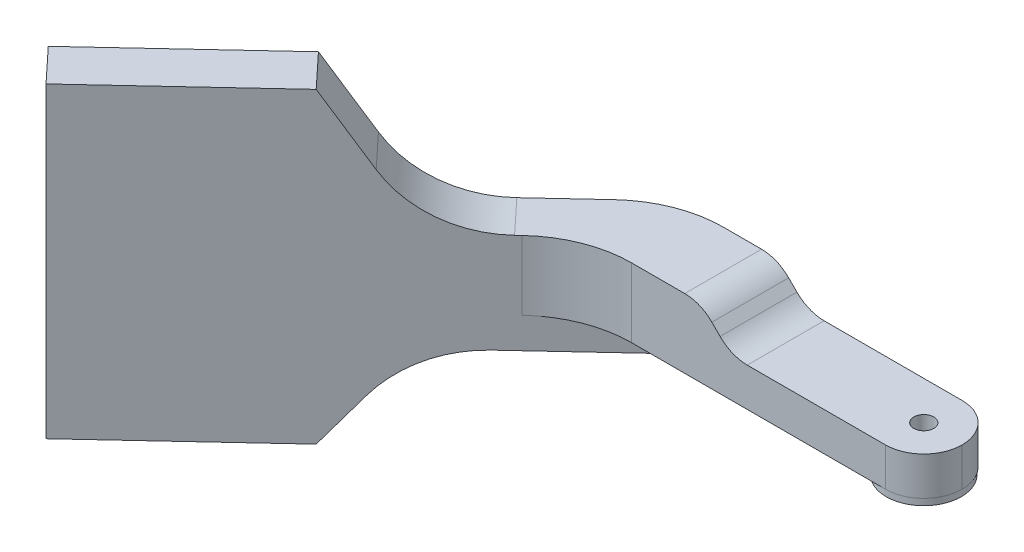
SolidWorks part; units mm, degrees
ref_plane "Front" through (0, 0, 0) normal (0, 0, 1) x (1, 0, 0)
ref_plane "Top" through (0, 0, 0) normal (0, 1, 0) x (1, 0, 0)
ref_plane "Right" through (0, 0, 0) normal (1, 0, 0) x (0, 0, -1)
sketch "Sketch1" plane through (0, 0, 0) normal (0, 1, 0) x (1, 0, 0)
  line L0 (0, 10) -> (0, 0)
  line L1 (0, 0) -> (42, 0)
  line L3 (0, 10) -> (42, 10)
  line L4 (42, 0) -> (42, 10)
  line L9 (0, 10) -> (-42.4185, -29.5559)
  line L10 (-42.4185, -29.5559) -> (-38.3265, -33.944)
  line L11 (0, 10) -> (4.092, 5.6119)
  line L12 (-38.3265, -33.944) -> (4.092, 5.6119)
  line L13 (0, 0) -> (-1.926, 0)
  line L14 (-1.926, 0) -> (0, 1.796)
  line L15 (0, 1.796) -> (0, 0)
  dimension "D1" = 10
  dimension "D2" = 42
  dimension "D3" = 223
  dimension "D4" = 58
  dimension "D5" = 6
  dimension "D6" = 270
extrude "Boss-Extrude1" add sketch "Sketch1" along normal blind 5 contours L10 L12 L1 L0 L9 | L1 L12 L11 L0 | L12 L1 L4 L3 L11 | L13 L0 L12 region at (1.364, 0, -5.8026) region at (-20.2035, 0, 12.8728) region at (21.8174, 0, -4.9666) region at (-0.642, 0, -0.5987)
fillet "Fillet1" radius 5 2 edges at (42, 2.5, 0) (42, 2.5, -10)
sketch "Sketch2" plane through (0, 5, 0) normal (0, 1, 0) x (1, 0, 0)
  circle A0 centre (37, 5) radius 1.3
extrude "Cut-Extrude1" cut sketch "Sketch2" against normal blind 10
sketch "Sketch3" plane through (0, 5, 0) normal (0, 1, 0) x (1, 0, 0)
  line L0 (-42.4185, -29.5559) -> (-38.3265, -33.944)
  line L1 (-38.3265, -33.944) -> (-20.1263, -16.972)
  line L2 (-38.3265, -33.944) -> (-1.926, 0) construction
  line L3 (-20.1263, -16.972) -> (-24.2183, -12.5839)
  line L4 (0, 10) -> (-42.4185, -29.5559) construction
  line L5 (-24.2183, -12.5839) -> (-42.4185, -29.5559)
extrude "Boss-Extrude2" add sketch "Sketch3" along normal blind 20
sketch "Sketch4" plane through (0, 0, 0) normal (0, -1, 0) x (1, 0, 0)
  line L0 (-42.4185, 29.5559) -> (-38.3265, 33.944)
  line L1 (-38.3265, 33.944) -> (-20.1263, 16.972)
  line L2 (-38.3265, 33.944) -> (-1.926, 0) construction
  line L3 (-20.1263, 16.972) -> (-24.2183, 12.5839)
  line L4 (0, -10) -> (-42.4185, 29.5559) construction
  line L5 (-24.2183, 12.5839) -> (-42.4185, 29.5559)
extrude "Boss-Extrude3" add sketch "Sketch4" along normal blind 15
sketch "Sketch5" plane through (-4.9878, 0, -5.3488) normal (-0.682, 0, -0.7314) x (-0.7314, 0, 0.682)
  line L0 (26.2943, -15) -> (26.2943, 0)
  line L1 (26.2943, 0) -> (13.889, 0)
  line L2 (-6.82, 0) -> (26.2943, 0) construction
  line L3 (13.889, 0) -> (26.2943, -15)
  line L4 (13.889, 5) -> (26.2943, 25)
  line L5 (-6.82, 5) -> (26.2943, 5) construction
  line L6 (26.2943, 25) -> (26.2943, 5)
  line L7 (26.2943, 5) -> (13.889, 5)
extrude "Boss-Extrude4" add sketch "Sketch5" against normal blind 6
sketch "Sketch6" plane through (0, 0, 0) normal (0, -1, 0) x (1, 0, 0)
  circle A0 centre (37, -5) radius 4.9
  circle A1 centre (37, -5) radius 1.3
extrude "Boss-Extrude5" add sketch "Sketch6" along normal blind 0.9
sketch "Sketch8" plane through (0, 0, 0) normal (0, -1, 0) x (1, 0, 0)
  line L0 (0, -10) -> (-19.6819, 8.3537)
  line L1 (-24.2183, 12.5839) -> (-15.1456, 4.1235) construction
  line L6 (-19.6819, 8.3537) -> (-15.5899, 12.7418)
  line L7 (-20.1263, 16.972) -> (-11.0536, 8.5116) construction
  line L8 (-15.5899, 12.7418) -> (8.7977, -10)
  line L9 (0, -10) -> (37, -10) construction
  line L10 (8.7977, -10) -> (0, -10)
extrude "Boss-Extrude6" add sketch "Sketch8" along normal blind 4
sketch "Sketch9" plane through (0, 5, 0) normal (0, 1, 0) x (1, 0, 0)
  line L3 (-17.565, -6.3796) -> (-24.2183, -12.5839) construction
  line L4 (-20.8916, -9.4817) -> (0, 10)
  line L6 (-20.8916, -9.4817) -> (-16.7996, -13.8699)
  line L7 (-20.1263, -16.972) -> (-11.0536, -8.5116) construction
  line L9 (-16.7996, -13.8699) -> (8.7977, 10)
  line L10 (0, 10) -> (37, 10) construction
  line L11 (8.7977, 10) -> (0, 10)
  line L12 (37, 0) -> (-1.926, 0) construction
  line L13 (8.7977, 0) -> (-1.926, 0)
  line L14 (-1.926, 0) -> (8.7977, 10)
  line L15 (8.7977, 10) -> (17.9505, 10)
  line L16 (17.9505, 10) -> (17.9505, 0)
  line L17 (17.9505, 0) -> (8.7977, 0)
  line M1 (-15.1456, -4.1235) -> (-11.0536, -8.5116)
  line M2 (-11.0536, -8.5116) -> (-1.926, 0)
  line M3 (-1.926, 0) -> (37, 0)
  line M6 (37, 10) -> (0, 10)
  line M7 (0, 10) -> (-15.1456, -4.1235)
extrude "Boss-Extrude7" add sketch "Sketch9" along normal blind 4 contours L9 M3 | L9 M2 M6 M7 M1 | L6 L9 L4 M1 region at (-15.9726, 5, 8.9967) region at (-4.2059, 5, -1.7921) region at (10.3631, 5, -4.3843)
fillet "Fillet2" radius 15 4 edges at (-15.519, -4, 8.5736) (-14.9141, 9, 8.0096) (-1.926, 4.5, 0) (0, 2.5, -10)
fillet "Fillet7" radius 5 1 edges at (17.9505, 9, -5) profile chamfer
fillet "Fillet8" radius 5 2 edges at (12.9505, 9, -5) (16.9505, 5, -5)
